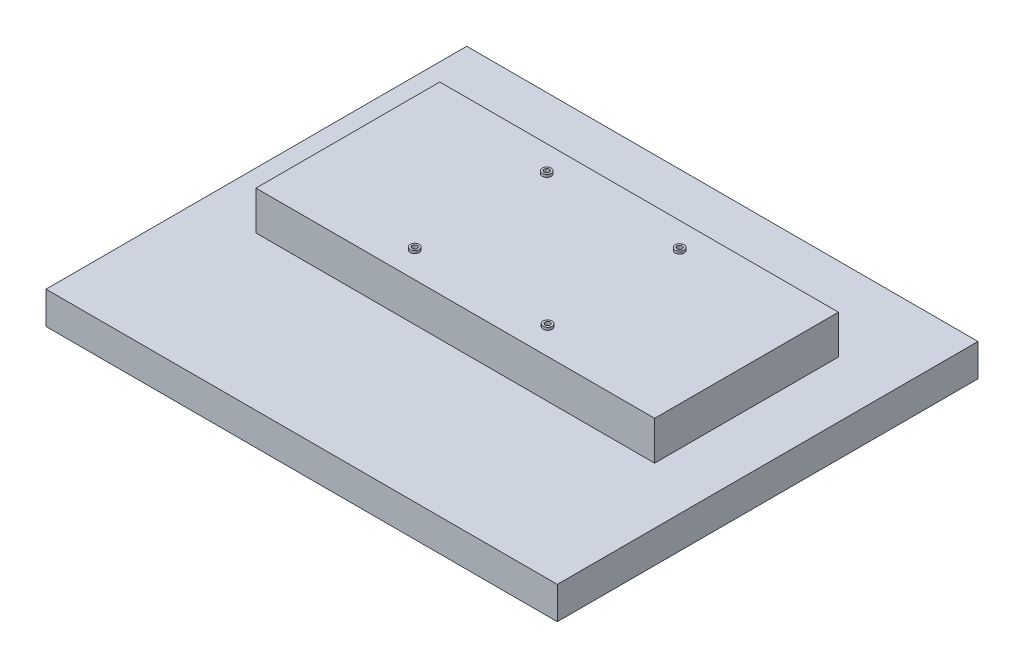
SolidWorks part; units mm, degrees
ref_plane "Front Plane" through (0, 0, 0) normal (0, 0, 1) x (1, 0, 0)
ref_plane "Top Plane" through (0, 0, 0) normal (0, 1, 0) x (1, 0, 0)
ref_plane "Right Plane" through (0, 0, 0) normal (1, 0, 0) x (0, 0, -1)
sketch "Sketch1" plane through (0, 0, 0) normal (0, 1, 0) x (1, 0, 0)
  line L1 (-197.5, -162.5) -> (197.5, -162.5)
  line L2 (-197.5, -162.5) -> (-197.5, 162.5)
  line L3 (-197.5, 162.5) -> (197.5, 162.5)
  line L4 (197.5, -162.5) -> (197.5, 162.5)
  line L5 (-197.5, -162.5) -> (197.5, 162.5) construction
  line L6 (-197.5, 162.5) -> (197.5, -162.5) construction
  point P0 (0, 0)
  dimension "D1" = 325
  dimension "D2" = 395
extrude "Boss-Extrude1" add sketch "Sketch1" along normal blind 25
sketch "Sketch2" plane through (0, 0, 0) normal (0, -1, 0) x (1, 0, 0)
  line L1 (-190, 152.5) -> (190, 152.5)
  line L2 (-190, 152.5) -> (-190, -152.5)
  line L3 (-190, -152.5) -> (190, -152.5)
  line L4 (190, 152.5) -> (190, -152.5)
  line L5 (-190, 152.5) -> (190, -152.5) construction
  line L6 (-190, -152.5) -> (190, 152.5) construction
  point P0 (0, 0)
  dimension "D1" = 305
  dimension "D2" = 380
extrude "Cut-Extrude1" cut sketch "Sketch2" against normal blind 0.8
sketch "Sketch3" plane through (0, 25, 0) normal (0, 1, 0) x (1, 0, 0)
  line L0 (0, 162.5) -> (0, 98.2) construction
  line L1 (197.5, 162.5) -> (-197.5, 162.5) construction
  line L2 (-154, 78.2) -> (-51.3333, 78.2) construction
  line L3 (-154, 98.2) -> (154, 98.2)
  line L4 (-154, 98.2) -> (-154, -43.8)
  line L5 (-154, -43.8) -> (154, -43.8)
  line L6 (154, 98.2) -> (154, -43.8)
  line L7 (-51.3333, 78.2) -> (-51.3333, 98.2) construction
  line L8 (0, 98.2) -> (0, -43.8) construction
  line L9 (-154, 27.2) -> (154, 27.2) construction
  circle A0 centre (-51.3333, 78.2) radius 3.5
  circle A1 centre (51.3333, 78.2) radius 3.5
  circle A2 centre (51.3333, -23.8) radius 3.5
  circle A3 centre (-51.3333, -23.8) radius 3.5
  point P9 (0, 98.2)
  dimension "D6" = 7
  dimension "D1" = 64.3
  dimension "D2" = 142
  dimension "D3" = 308
  dimension "D4" = 102.6667
  dimension "D5" = 20
extrude "Boss-Extrude3" add sketch "Sketch3" along normal blind 30 contours L6 L3 L4 L5 A1 A0 A2 A3 region at (0, 25, -27.2)
extrude "Boss-Extrude4" add sketch "Sketch3<3>" along normal blind 32 contours A3 | A2 | A1 | A0 region at (-51.3333, 25, -78.2) region at (51.3333, 25, -78.2) region at (51.3333, 25, 23.8) region at (-51.3333, 25, 23.8)
sketch "Sketch3<3>" plane through (0, 25, 0) normal (0, 1, 0) x (1, 0, 0) same geometry as "Sketch3"
sketch "Sketch4" plane through (0, 57, 0) normal (0, 1, 0) x (1, 0, 0)
  circle A0 centre (-51.3333, 78.2) radius 2
  circle A1 centre (51.3333, 78.2) radius 2
  circle A2 centre (-51.3333, -23.8) radius 2
  circle A3 centre (51.3333, -23.8) radius 2
  dimension "D1" = 4
  dimension "D2" = 4
  dimension "D3" = 4
  dimension "D4" = 4
extrude "Cut-Extrude2" cut sketch "Sketch4" against normal blind 10
